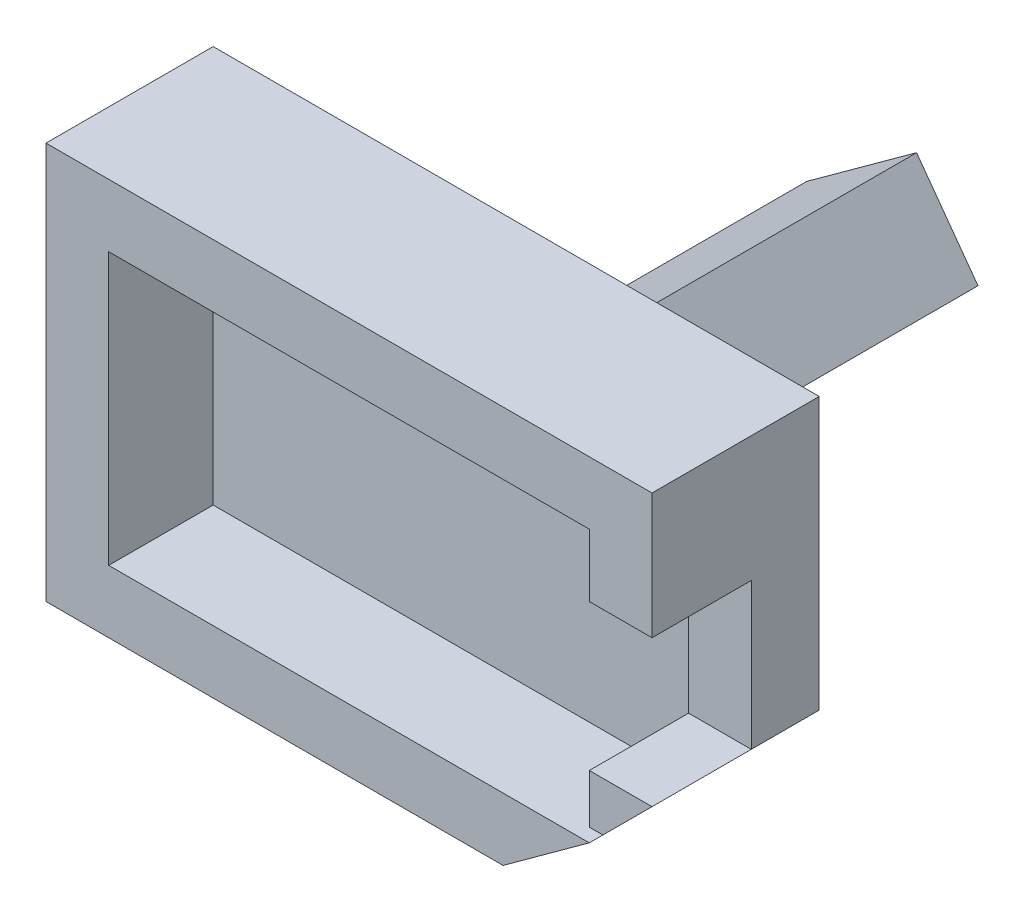
SolidWorks part; units mm, degrees
ref_plane "Front Plane" through (0, 0, 0) normal (0, 0, 1) x (1, 0, 0)
ref_plane "Top Plane" through (0, 0, 0) normal (0, 1, 0) x (1, 0, 0)
ref_plane "Right Plane" through (0, 0, 0) normal (1, 0, 0) x (0, 0, -1)
sketch "Sketch1" plane through (0, 0, 0) normal (0, 0, 1) x (1, 0, 0)
  line L0 (7.3709, -9.5) -> (-14.5, -9.5)
  line L1 (11.5, -6.5) -> (-11.5, -6.5) construction
  line L2 (11.5, -6.5) -> (11.5, 6.5) construction
  line L3 (11.5, 6.5) -> (-11.5, 6.5) construction
  line L4 (-11.5, -6.5) -> (-11.5, 6.5) construction
  line L5 (11.5, -6.5) -> (-11.5, 6.5) construction
  line L6 (11.5, 6.5) -> (-11.5, -6.5) construction
  line L7 (-14.5, -9.5) -> (-14.5, 9.5)
  line L8 (14.5, 9.5) -> (-14.5, 9.5)
  line L9 (14.5, -3.5) -> (14.5, 9.5)
  line L10 (14.5, -3.5) -> (11.5, -6.5)
  line L12 (7.3709, -9.5) -> (11.5, -6.5)
  line L13 (14.5, -9.5) -> (14.5, 9.5) construction
  line L14 (14.5, -9.5) -> (-14.5, -9.5) construction
  point P0 (0, 0)
  dimension "D1" = 13
  dimension "D2" = 23
  dimension "D4" = 45
  dimension "D5" = 36
  dimension "D3" = 3
extrude "Boss-Extrude1" add sketch "Sketch1" along normal blind 3
sketch "Sketch2" plane through (0, 0, 3) normal (0, 0, 1) x (1, 0, 0)
  line L0 (14.5, -3.5) -> (12.1512, -5.8488)
  line L1 (11.5, -6.5) -> (-11.5, -6.5)
  line L2 (11.5, -5.8488) -> (11.5, 6.5)
  line L3 (11.5, 6.5) -> (-11.5, 6.5)
  line L4 (-11.5, -6.5) -> (-11.5, 6.5)
  line L5 (11.5, -6.5) -> (-11.5, 6.5) construction
  line L6 (11.5, 6.5) -> (-11.5, -6.5) construction
  line L7 (7.3709, -9.5) -> (-14.5, -9.5)
  line L8 (14.5, -3.5) -> (14.5, 9.5)
  line L9 (14.5, 9.5) -> (-14.5, 9.5)
  line L10 (-14.5, -9.5) -> (-14.5, 9.5)
  line L11 (14.5, -9.5) -> (-14.5, 9.5) construction
  line L12 (14.5, 9.5) -> (-14.5, -9.5) construction
  line L13 (11.5, -5.8488) -> (12.1512, -5.8488)
  line L14 (11.5, -6.5) -> (7.3709, -9.5)
  point P0 (0, 0)
  point P7 (0, 0)
  point P21 (0, 0)
  dimension "D1" = 2.3488
  dimension "D2" = 45
  dimension "D3" = 13
  dimension "D4" = 5.1039
extrude "Boss-Extrude2" add sketch "Sketch2" along normal blind 5
sketch "Sketch3" plane through (0, 0, 0) normal (0, 0, -1) x (-1, 0, 0)
  line L0 (0, 0) -> (5.8546, 0) construction
  line L1 (-1.1598, 3.9328) -> (4.0988, 0.1122)
  line L2 (-1.1598, 3.9328) -> (-4.0988, -0.1122)
  line L3 (-4.0988, -0.1122) -> (1.1598, -3.9328)
  line L4 (4.0988, 0.1122) -> (1.1598, -3.9328)
  line L5 (-1.1598, 3.9328) -> (1.1598, -3.9328) construction
  line L6 (-4.0988, -0.1122) -> (4.0988, 0.1122) construction
  line L7 (0, 0) -> (4.1972, -3.0495) construction
  point P0 (0, 0)
  dimension "D1" = 36
  dimension "D2" = 5
  dimension "D3" = 5.188
  dimension "D4" = 6.5
extrude "Boss-Extrude3" add sketch "Sketch3" along normal blind 18
sketch "Sketch4" plane through (14.5, 0, 0) normal (1, 0, 0) x (0, 0, -1)
  line L0 (0, 0) -> (-4, 0) construction
  line L1 (-8, 3.5) -> (-8, -3.5)
  line L2 (-3.25, -3.5) -> (-8, -3.5)
  line L3 (-3.25, -3.5) -> (-3.25, 3.5)
  line L4 (-3.25, 3.5) -> (-8, 3.5)
  dimension "D1" = 4
  dimension "D2" = 0.75
  dimension "D3" = 7
  dimension "D4" = 4.75
extrude "Cut-Extrude1" cut sketch "Sketch4" against normal blind 8
